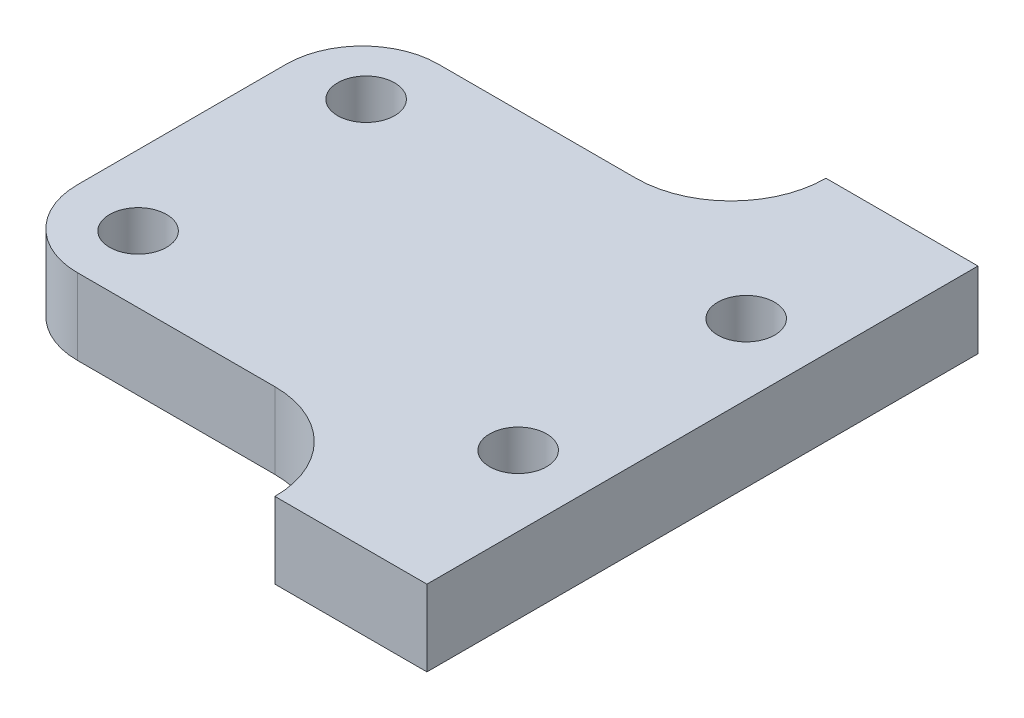
SolidWorks part; units mm, degrees
material "合金钢"
ref_plane "前视基准面" through (0, 0, 0) normal (0, 0, 1) x (1, 0, 0)
ref_plane "上视基准面" through (0, 0, 0) normal (0, 1, 0) x (1, 0, 0)
ref_plane "右视基准面" through (0, 0, 0) normal (1, 0, 0) x (0, 0, -1)
sketch "草图1" plane through (0, 0, 0) normal (0, 0, 1) x (1, 0, 0)
  line L0 (-0.6404, -1.8816) -> (-1.6404, -1.8816)
  line L1 (24.7596, -1.8816) -> (25.7596, -1.8816)
  line L2 (-1.6404, -1.8816) -> (-1.6404, -2.8816)
  line L3 (-1.6404, -2.8816) -> (25.7596, -2.8816)
  line L4 (25.7596, -2.8816) -> (25.7596, -1.8816)
  line L5 (-1.6404, -2.8816) -> (-1.6404, -6.8816)
  line L6 (-1.6404, -6.8816) -> (25.7596, -6.8816)
  line L7 (25.7596, -6.8816) -> (25.7596, -1.8816)
  arc A0 (4.0971, -0.5771) -> (3.4439, 1.2653) centre (-3.2619, -2.1492) ccw
  arc A1 (4.0971, -0.5771) -> (5.4066, -1.8535) centre (5.7096, -0.2326) ccw
  arc A2 (0.9722, -0.5771) -> (1.6254, 1.2653) centre (8.3312, -2.1492) cw
  arc A3 (0.9722, -0.5771) -> (-0.3374, -1.8535) centre (-0.6404, -0.2326) cw
  arc A4 (3.4439, 1.2653) -> (1.6254, 1.2653) centre (2.5346, -17.2174) ccw
  arc A5 (10.4471, -0.5771) -> (9.7939, 1.2653) centre (3.0881, -2.1492) ccw
  arc A6 (10.4471, -0.5771) -> (11.7566, -1.8535) centre (12.0596, -0.2326) ccw
  arc A7 (7.3222, -0.5771) -> (7.9754, 1.2653) centre (14.6812, -2.1492) cw
  arc A8 (7.3222, -0.5771) -> (6.0126, -1.8535) centre (5.7096, -0.2326) cw
  arc A9 (9.7939, 1.2653) -> (7.9754, 1.2653) centre (8.8846, -17.2174) ccw
  arc A10 (16.7971, -0.5771) -> (16.1439, 1.2653) centre (9.4381, -2.1492) ccw
  arc A11 (16.7971, -0.5771) -> (18.1066, -1.8535) centre (18.4096, -0.2326) ccw
  arc A12 (13.6722, -0.5771) -> (14.3254, 1.2653) centre (21.0312, -2.1492) cw
  arc A13 (13.6722, -0.5771) -> (12.3626, -1.8535) centre (12.0596, -0.2326) cw
  arc A14 (16.1439, 1.2653) -> (14.3254, 1.2653) centre (15.2346, -17.2174) ccw
  arc A15 (23.1471, -0.5771) -> (22.4939, 1.2653) centre (15.7881, -2.1492) ccw
  arc A16 (23.1471, -0.5771) -> (24.4566, -1.8535) centre (24.7596, -0.2326) ccw
  arc A17 (20.0222, -0.5771) -> (20.6754, 1.2653) centre (27.3812, -2.1492) cw
  arc A18 (20.0222, -0.5771) -> (18.7126, -1.8535) centre (18.4096, -0.2326) cw
  arc A19 (22.4939, 1.2653) -> (20.6754, 1.2653) centre (21.5846, -17.2174) ccw
  arc A20 (6.0126, -1.8535) -> (5.4066, -1.8535) centre (5.7096, -0.2326) cw
  arc A21 (12.3626, -1.8535) -> (11.7566, -1.8535) centre (12.0596, -0.2326) cw
  arc A22 (18.1066, -1.8535) -> (18.7126, -1.8535) centre (18.4096, -0.2326) ccw
  arc A23 (-0.6404, -1.8816) -> (0.9722, -0.5771) centre (-0.6404, -0.2326) ccw
  arc A24 (23.1471, -0.5771) -> (24.7596, -1.8816) centre (24.7596, -0.2326) ccw
  dimension "D2" = 1
  dimension "D3" = 1
  dimension "D4" = 1
  dimension "D5" = 4
  dimension "D1" = 4
extrude "凸台-拉伸1" add sketch "草图1" along normal blind 3 contours A24 A16 A15 A19 A17 A18 A22 A11 A10 A14 A12 A13 A21 A6 A5 A9 A7 A8 A20 A1 A0 A4 A2 A3 A23 L0 L2 L3 L4 L1 | L6 L7 L3 L5 region at (-0.4626, -2.1505, 0) region at (12.0596, -4.8816, 0)
extrude "凸台-拉伸2" add sketch "草图1<3>" along normal blind 11 contours L6 L7 L3 L5 region at (12.0596, -4.8816, 0)
sketch "草图1<3>" plane through (0, 0, 0) normal (0, 0, 1) x (1, 0, 0) same geometry as "草图1"
extrude "凸台-拉伸3" add sketch "草图1<4>" against normal blind 8 contours L6 L7 L3 L5 region at (12.0596, -4.8816, 0)
sketch "草图1<4>" plane through (0, 0, 0) normal (0, 0, 1) x (1, 0, 0) same geometry as "草图1"
sketch "草图2" plane through (0, -2.8816, 0) normal (0, 1, 0) x (1, 0, 0)
  line L0 (12.0596, 8) -> (12.0596, -11) construction
  line L1 (-1.6404, 8) -> (25.7596, 8) construction
  line L2 (-1.6404, -11) -> (25.7596, -11) construction
  line L4 (2.0596, -7.5) -> (22.0596, -7.5) construction
  line L5 (2.0596, -7.5) -> (2.0596, 4.5) construction
  line L6 (2.0596, 4.5) -> (22.0596, 4.5) construction
  line L7 (22.0596, -7.5) -> (22.0596, 4.5) construction
  line L8 (2.0596, -7.5) -> (22.0596, 4.5) construction
  line L9 (2.0596, 4.5) -> (22.0596, -7.5) construction
  circle A0 centre (2.0596, 4.5) radius 1.5
  circle A1 centre (22.0596, 4.5) radius 1.5
  circle A2 centre (22.0596, -7.5) radius 1.5
  circle A3 centre (2.0596, -7.5) radius 1.5
  point P6 (12.0596, -1.5)
  dimension "D3" = 3
  dimension "D4" = 3
  dimension "D5" = 3
  dimension "D6" = 3
  dimension "D1" = 12
  dimension "D2" = 20
extrude "切除-拉伸1" cut sketch "草图2" against normal blind 6.5
fillet "圆角1" radius 4 2 edges at (-1.6404, -4.8816, -8) (-1.6404, -4.8816, 11)
sketch "草图4" plane through (0, 0, -8) normal (0, 0, -1) x (-1, 0, 0)
  line L0 (-14.0596, -6.8816) -> (-14.0596, -11.8816) construction
  line L1 (-2.3596, -6.8816) -> (-25.7596, -6.8816) construction
  line L2 (-14.0596, -6.8816) -> (-11.5596, -6.8816) construction
  line L3 (-11.5596, -12.8816) -> (-4.5596, -12.8816) construction
  line L4 (-11.5596, -6.8816) -> (-16.5596, -6.8816)
  line L5 (-11.5596, -6.8816) -> (-11.5596, -12.8816)
  line L7 (-16.5596, -6.8816) -> (-16.5596, -12.8816)
  line L8 (-11.5596, -12.8816) -> (-7.5596, -12.8816) construction
  line L9 (-2.6366, -19.6122) -> (-2.6366, -20.4157)
  arc A0 (-11.5596, -12.8816) -> (-2.6366, -19.6122) centre (-4.5596, -12.8816) ccw
  arc A1 (-16.5596, -12.8816) -> (-2.6366, -20.4157) centre (-7.5596, -12.8816) ccw
  dimension "D1" = 5
  dimension "D2" = 2.5
  dimension "D3" = 6
  dimension "D4" = 5
  dimension "D5" = 7
  dimension "D6" = 9
extrude "凸台-拉伸4" add sketch "草图4" against normal up to surface (19 mm away) up to face at (14.0596, -4.8816, 11)
sketch "草图6" plane through (0, -6.8816, 0) normal (0, -1, 0) x (1, 0, 0)
  line L1 (-2.723, 12.3626) -> (29.5343, 12.3626)
  line L2 (-2.723, 12.3626) -> (-2.723, -11.3462)
  line L3 (-2.723, -11.3462) -> (29.5343, -11.3462)
  line L4 (29.5343, 12.3626) -> (29.5343, -11.3462)
extrude "切除-拉伸2" cut sketch "草图6" along normal blind 21
sketch "草图7" plane through (0, 0, 11) normal (0, 0, 1) x (1, 0, 0)
  line L1 (25.7596, -6.8816) -> (17.7596, -6.8816)
  line L2 (25.7596, -6.8816) -> (25.7596, -2.8816)
  line L3 (25.7596, -2.8816) -> (17.7596, -2.8816)
  line L4 (17.7596, -6.8816) -> (17.7596, -2.8816)
  line L5 (25.7596, -2.8816) -> (-1.6404, -2.8816) construction
  point P6 (14.0596, -4.8816)
  dimension "D1" = 4
  dimension "D2" = 8
extrude "凸台-拉伸5" add sketch "草图7" along normal blind 5
sketch "草图8" plane through (0, 0, -8) normal (0, 0, -1) x (-1, 0, 0)
  line L12 (-25.7596, -2.8816) -> (-17.7596, -2.8816)
  line L13 (-25.7596, -2.8816) -> (-25.7596, -6.8816)
  line L14 (-25.7596, -6.8816) -> (-17.7596, -6.8816)
  line L15 (-17.7596, -2.8816) -> (-17.7596, -6.8816)
  point P6 (-12.0596, -4.8816)
  dimension "D1" = 4
  dimension "D2" = 8
extrude "凸台-拉伸6" add sketch "草图8" along normal blind 5
sketch "草图9" plane through (0, -2.8816, 0) normal (0, 1, 0) x (1, 0, 0)
  line L1 (-12.8044, 14.4468) -> (34.4042, 14.4468)
  line L2 (-12.8044, 14.4468) -> (-12.8044, -16.2062)
  line L3 (-12.8044, -16.2062) -> (34.4042, -16.2062)
  line L4 (34.4042, 14.4468) -> (34.4042, -16.2062)
extrude "切除-拉伸3" cut sketch "草图9" along normal blind 18
fillet "圆角2" radius 5 2 edges at (17.7596, -4.8816, 11) (17.7596, -4.8816, -8)
